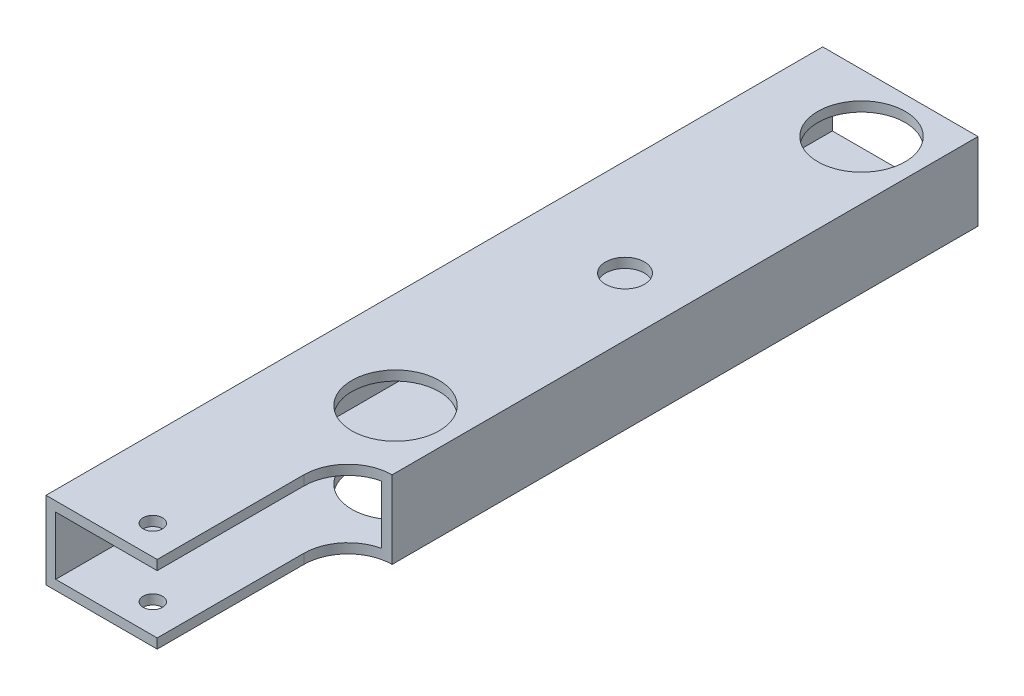
SolidWorks part; units mm, degrees
material "6063-T6"
ref_plane "Front" through (0, 0, 0) normal (0, 0, 1) x (1, 0, 0)
ref_plane "Top" through (0, 0, 0) normal (0, 1, 0) x (1, 0, 0)
ref_plane "Right" through (0, 0, 0) normal (1, 0, 0) x (0, 0, -1)
sketch "Sketch1" plane through (0, 0, 0) normal (0, 0, 1) x (1, 0, 0)
  line L0 (3.175, 3.175) -> (47.625, 3.175)
  line L1 (0, 0) -> (50.8, 0)
  line L2 (0, 0) -> (0, 25.4)
  line L3 (0, 25.4) -> (50.8, 25.4)
  line L4 (50.8, 0) -> (50.8, 25.4)
  line L5 (47.625, 3.175) -> (47.625, 22.225)
  line L6 (3.175, 22.225) -> (47.625, 22.225)
  line L7 (3.175, 3.175) -> (3.175, 22.225)
  dimension "D1" = 25.4
  dimension "D2" = 50.8
  dimension "D3" = 3.175
extrude "Boss-Extrude1" add sketch "Sketch1" along normal blind 254
sketch "Sketch2" plane through (0, 25.4, 0) normal (0, 1, 0) x (1, 0, 0)
  line L0 (31.75, 0) -> (31.75, -19.05) construction
  line L2 (31.75, -19.05) -> (31.75, -171.45) construction
  line L4 (50.8, -254) -> (50.8, 0) construction
  line L5 (50.8, 0) -> (0, 0) construction
  circle A0 centre (31.75, -19.05) radius 14.2875
  circle A1 centre (31.75, -171.45) radius 14.2875
  dimension "D1" = 28.575
  dimension "D4" = 28.575
  dimension "D2" = 19.05
  dimension "D3" = 152.4
  dimension "D5" = 19.05
extrude "Cut-Extrude1" cut sketch "Sketch2" against normal through all
sketch "Sketch3" plane through (0, 25.4, 0) normal (0, 1, 0) x (1, 0, 0)
  line L0 (25.4, -244.475) -> (25.4, -254) construction
  line L1 (50.8, -254) -> (0, -254) construction
  circle A0 centre (25.4, -244.475) radius 3.175
  dimension "D1" = 6.35
  dimension "D2" = 9.525
extrude "Cut-Extrude2" cut sketch "Sketch3" against normal through all
sketch "Sketch4" plane through (0, 25.4, 0) normal (0, 1, 0) x (1, 0, 0)
  line L0 (36.3589, -254) -> (36.3589, -206.0354)
  line L1 (50.8, -254) -> (0, -254) construction
  line L2 (50.8, -191.5943) -> (50.8, -254)
  line L3 (50.8, -254) -> (50.8, 0) construction
  line L4 (50.8, -254) -> (36.3589, -254)
  arc A0 (50.8, -191.5943) -> (36.3589, -206.0354) centre (50.8, -206.0354) ccw
extrude "Cut-Extrude3" cut sketch "Sketch4" against normal through all
sketch "Sketch5" plane through (0, 0, 0) normal (0, -1, 0) x (1, 0, 0)
  circle A0 centre (31.75, 95.25) radius 2.667 construction
  circle A1 centre (31.75, 95.25) radius 2.667
extrude "Cut-Extrude4" cut sketch "Sketch5" against normal through all
sketch "Sketch6" plane through (0, 25.4, 0) normal (0, 1, 0) x (1, 0, 0)
  circle A0 centre (31.75, -96.3958) radius 6.35
  dimension "D1" = 12.7
extrude "Cut-Extrude5" cut sketch "Sketch6" against normal up to next
